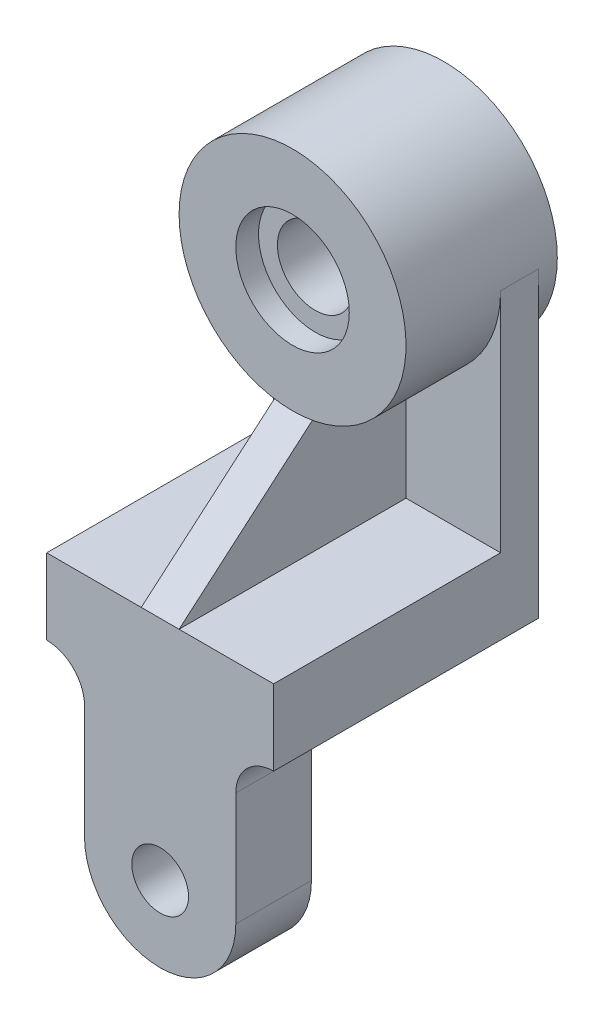
SolidWorks part; units mm, degrees
ref_plane "Front Plane" through (0, 0, 0) normal (0, 0, 1) x (1, 0, 0)
ref_plane "Top Plane" through (0, 0, 0) normal (0, 1, 0) x (1, 0, 0)
ref_plane "Right Plane" through (0, 0, 0) normal (1, 0, 0) x (0, 0, -1)
sketch "Sketch1" plane through (0, 0, 0) normal (0, 1, 0) x (1, 0, 0)
  line L1 (-30, 35) -> (30, 35)
  line L2 (-30, 35) -> (-30, -35)
  line L3 (-30, -35) -> (30, -35)
  line L4 (30, 35) -> (30, -35)
  line L5 (-30, 35) -> (30, -35) construction
  line L6 (-30, -35) -> (30, 35) construction
  point P0 (0, 0)
  dimension "D1" = 70
  dimension "D2" = 60
extrude "Boss-Extrude1" add sketch "Sketch1" along normal blind 20
sketch "Sketch2" plane through (0, 0, 35) normal (0, 0, 1) x (1, 0, 0)
  line L0 (-20, 0) -> (20, 0)
  line L1 (-20, 0) -> (-20, -40)
  line L2 (20, 0) -> (20, -40)
  line L3 (-20, -40) -> (20, -40)
  line L4 (-30, 0) -> (30, 0) construction
  arc A0 (-20, -40) -> (20, -40) centre (0, -40) ccw
  circle A1 centre (0, -40) radius 7.5
  line M7 (-30, 0) -> (30, 0)
  dimension "D4" = 15
  dimension "D1" = 10
  dimension "D2" = 40
  dimension "D3" = 40
extrude "Boss-Extrude2" add sketch "Sketch2" against normal blind 20 contours A1 L3 A0 | A1 L3 L2 L1 M7 region at (0, -19.017, 35) region at (0, -49.3564, 35)
sketch "Sketch3" plane through (0, 0, -35) normal (0, 0, -1) x (-1, 0, 0)
  line L0 (0, 20) -> (0, 80) construction
  line L1 (-30, 20) -> (30, 20) construction
  line L2 (-30, 20) -> (30, 20)
  line L3 (-30, 20) -> (-30, 80)
  line L4 (30, 20) -> (30, 80)
  line L5 (-30, 80) -> (30, 80)
  circle A0 centre (0, 80) radius 30
  circle A1 centre (0, 80) radius 15
  circle A2 centre (0, 80) radius 10
  line M4 (30, 20) -> (-30, 20)
  dimension "D2" = 60
  dimension "D3" = 30
  dimension "D4" = 20
  dimension "D1" = 60
extrude "Boss-Extrude3" add sketch "Sketch3" against normal blind 10 contours L2 L0 A0 L3 | L0 L4 A0 M4 region at (16.4663, 38.8342, -35) region at (-16.4663, 38.8342, -35)
extrude "Boss-Extrude4" add sketch "Sketch3<3>" along normal blind 5 separate body contours A0
sketch "Sketch3<3>" plane through (0, 0, -35) normal (0, 0, -1) x (-1, 0, 0) same geometry as "Sketch3"
extrude "Boss-Extrude5" add sketch "Sketch3<4>" against normal blind 35 contours A0
sketch "Sketch3<4>" plane through (0, 0, -35) normal (0, 0, -1) x (-1, 0, 0) same geometry as "Sketch3"
sketch "Sketch4" plane through (0, 0, 0) normal (0, 0, 1) x (1, 0, 0)
  circle A0 centre (0, 80) radius 10 construction
  circle A1 centre (0, 80) radius 30
  circle A2 centre (0, 80) radius 30
  circle A3 centre (0, 80) radius 15 construction
  circle A4 centre (0, 80) radius 10
  circle A5 centre (0, 80) radius 15
  dimension "D1" = 0
extrude "Cut-Extrude1" cut sketch "Sketch4" against normal blind 6 contours A5
extrude "Cut-Extrude2" cut sketch "Sketch4<3>" against normal through all contours A4
sketch "Sketch4<3>" plane through (0, 0, 0) normal (0, 0, 1) x (1, 0, 0) same geometry as "Sketch4"
sketch "Sketch5" plane through (0, 0, 0) normal (1, 0, 0) x (0, 0, -1)
  line L0 (0, 50) -> (-35, 20)
  point P3 (0, 0)
rib "Rib1" sketch "Sketch5" sketch "Sketch5" thickness 10 extrusion direction parallel to sketch draft on no parameters "D1"=10
fillet "Fillet1" radius 10 2 edges at (-20, 0, 25) (20, 0, 25)
